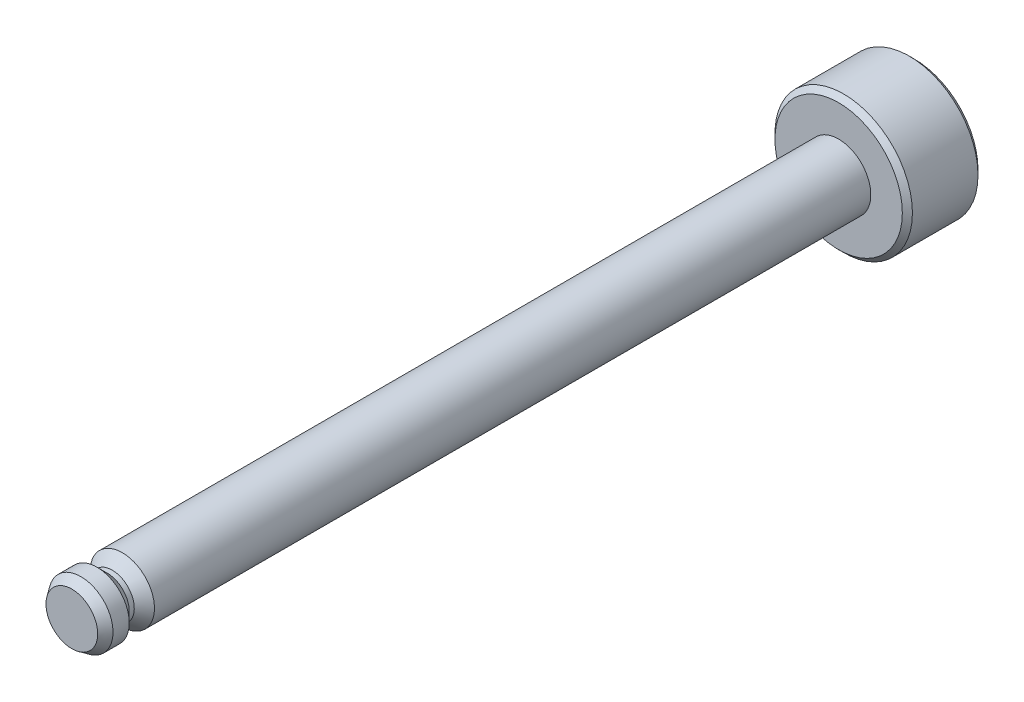
SolidWorks part; units mm, degrees
ref_plane "Front" through (0, 0, 0) normal (0, 0, 1) x (1, 0, 0)
ref_plane "Top" through (0, 0, 0) normal (0, 1, 0) x (1, 0, 0)
ref_plane "Right" through (0, 0, 0) normal (1, 0, 0) x (0, 0, -1)
sketch "Sketch2" plane through (0, 0, 0) normal (0, 0, 1) x (1, 0, 0)
  circle A0 centre (0, 0) radius 1.275
  dimension "D1" = 2.55
extrude "Shaft" add sketch "Sketch2" along normal blind 30.4
sketch "Sketch5" plane through (0, 0, 0) normal (0, 0, 1) x (1, 0, 0)
  circle A0 centre (0, 0) radius 2.725
  dimension "D1" = 5.45
extrude "Head" add sketch "Sketch5" against normal blind 3
chamfer "Chamfer1" distance 0.25 angle 55 1 edges at (1.275, 0, 30.4) first distance on face at (1.275, 0, 30.4)
chamfer "Deburs" distance 0.2 angle 45 2 edges at (2.725, 0, 0) (2.725, 0, -3)
sketch "Sketch6" plane through (0, 0, 0) normal (1, 0, 0) x (0, 0, -1)
  line L0 (0, 0) -> (-28.9, 0) construction
  line L1 (-28.9, 0) -> (-28.9, 0.875) construction
  line L2 (0, 1.275) -> (-30.043, 1.275) construction
  line L3 (-29.4, 1.275) -> (-28.4, 1.275)
  line L4 (-28.4, 1.275) -> (-28.8, 0.875)
  line L5 (-28.8, 0.875) -> (-29, 0.875)
  line L6 (-29, 0.875) -> (-29.4, 1.275)
  line L7 (-28.9, 0.875) -> (-28.9, 1.275) construction
  dimension "D1" = 28.9
  dimension "D2" = 0.4
  dimension "D3" = 1
revolve "e-Clip Notch Long" cut sketch "Sketch6" angle 360 about L0
equation "\"D1@Sketch2\"=\"Plastic Hardware OD@Box Assy.Assembly\""
equation "\"D1\"= \"Countersink Diameter@Box Assy.Assembly\" - .3mm"
equation "\"D1@Head\"=\"Countersink Depth@Box Assy.Assembly\""
equation "\"Length\"= 30mm"
equation "\"D1@Shaft\"=\"Length\"+.4mm"
equation "\"D1@Sketch6\"=\"Length\"-1.1mm"
